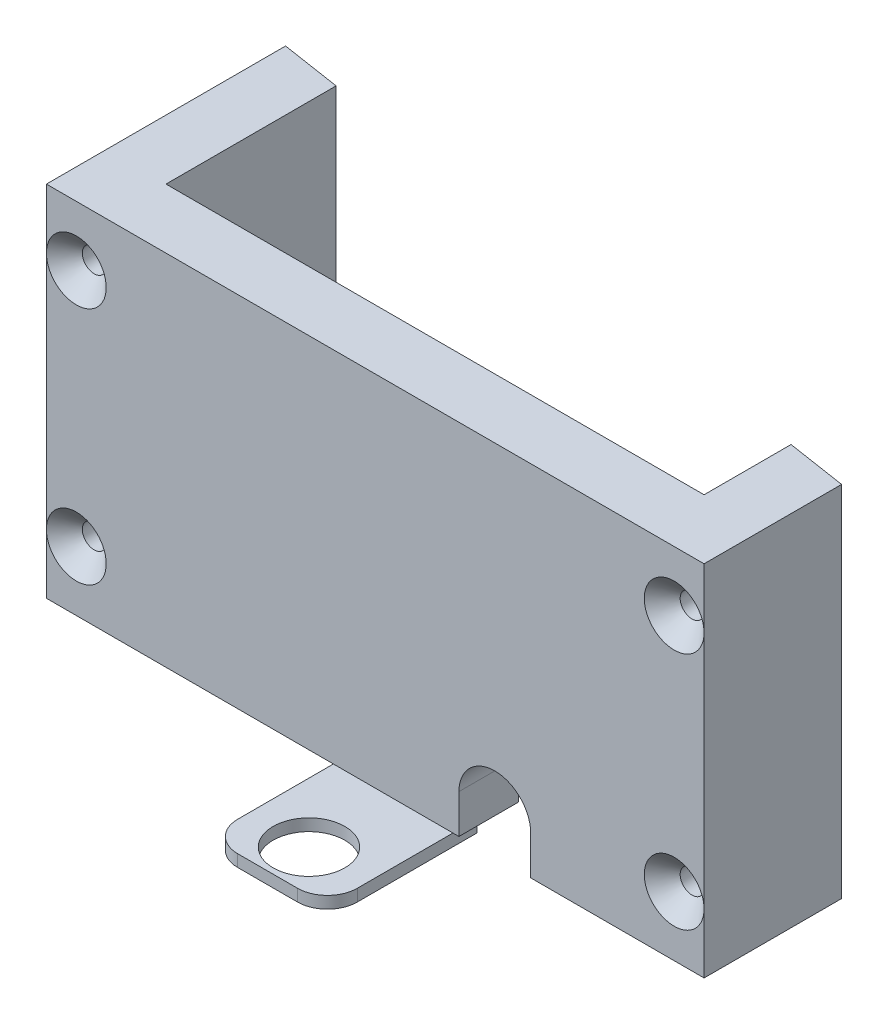
SolidWorks part; units mm, degrees
ref_plane "Plan de face" through (0, 0, 0) normal (0, 0, 1) x (1, 0, 0)
ref_plane "Plan de dessus" through (0, 0, 0) normal (0, 1, 0) x (1, 0, 0)
ref_plane "Plan de droite" through (0, 0, 0) normal (1, 0, 0) x (0, 0, -1)
sketch "Esquisse1" plane through (0, 0, 0) normal (0, 0, 1) x (1, 0, 0)
  line L1 (0, 0) -> (110, 0)
  line L2 (0, 0) -> (0, -60)
  line L3 (0, -60) -> (110, -60)
  line L4 (110, 0) -> (110, -60)
  dimension "D1" = 110
  dimension "D2" = 60
extrude "Boss.-Extru.1" add sketch "Esquisse1" along normal blind 10
sketch "Esquisse3" plane through (0, 0, 10) normal (0, 0, 1) x (1, 0, 0)
  line L0 (81, -53.5) -> (81, -60)
  line L3 (73.1533, -49.5) -> (73.1533, -57.5) construction
  line L4 (84.5, -49.5) -> (24.5, -49.5) construction
  line L5 (84.5, -57.5) -> (24.5, -57.5) construction
  line L7 (110, -60) -> (110, 0) construction
  line L8 (0, -60) -> (110, -60) construction
  line L9 (81, -60) -> (69, -60)
  line L10 (69, -60) -> (69, -53.5)
  arc A1 (81, -53.5) -> (69, -53.5) centre (75, -53.5) ccw
  dimension "D1" = 12
  dimension "D3" = 35
sketch "Esquisse7" plane through (0, 0, 0) normal (0, 0, -1) x (-1, 0, 0)
  line L0 (0, -60) -> (-110, -60) construction
  line L1 (-110, 0) -> (-100, 0)
  line L2 (-110, 0) -> (-110, -60)
  line L3 (-110, -60) -> (-100, -60)
  line L4 (-100, 0) -> (-100, -60)
  line L6 (0, 0) -> (-10, 0)
  line L7 (0, 0) -> (0, -60)
  line L8 (0, -60) -> (-10, -60)
  line L9 (-10, 0) -> (-10, -60)
  dimension "D1" = 10
extrude "Boss.-Extru.3" add sketch "Esquisse7" along normal blind 30
sketch "Esquisse8" plane through (0, -60, 0) normal (0, -1, 0) x (1, 0, 0)
  line L4 (0, -30) -> (110, -13)
  line L5 (110, 10) -> (110, -30) construction
  line L6 (110, -13) -> (110, -30)
  line L7 (110, -30) -> (0, -30)
  dimension "D1" = 17
extrude "Enlèv. mat.-Extru.2" cut sketch "Esquisse8" against normal blind 81
sketch "Esquisse9" plane through (0, 0, 10) normal (0, 0, 1) x (1, 0, 0)
  line L0 (0, 0) -> (0, -60) construction
  line L1 (110, -60) -> (110, 0) construction
  line L2 (110, 0) -> (0, 0) construction
  line L3 (0, -60) -> (110, -60) construction
  circle A0 centre (5, -10) radius 2
  circle A1 centre (105, -10) radius 2
  circle A2 centre (105, -50) radius 2
  circle A3 centre (5, -50) radius 2
  dimension "D1" = 4
  dimension "D2" = 5
  dimension "D3" = 5
  dimension "D4" = 5
  dimension "D5" = 5
  dimension "D6" = 10
  dimension "D7" = 10
  dimension "D8" = 10
  dimension "D9" = 10
extrude "Enlèv. mat.-Extru.3" cut sketch "Esquisse9" against normal through all
chamfer "Chanfrein1" distance 3 angle 45 4 edges at (107, -10, 10) (107, -50, 10) (7, -50, 10) (7, -10, 10)
extrude "Enlèv. mat.-Extru.4" cut sketch "Esquisse3" against normal blind 10
ref_plane "Plan1" through (85, 0, 0) normal (-1, 0, 0) x (0, 0, 1)
sketch "Esquisse10" plane through (85, 0, 0) normal (-1, 0, 0) x (0, 0, 1)
  line L3 (-5.5213, -1.3552) -> (-6.7343, -1.3552)
  line L8 (0, -24.6816) -> (0, -42)
  line L9 (0, -60) -> (0, 0) construction
  line L10 (0, -42) -> (-7.5577, -42)
  line L11 (-7.5577, -42) -> (-7.5577, -62.3933)
  line L12 (-7.5577, -62.3933) -> (-9.5577, -62.3933)
  line L13 (-9.5577, -62.3933) -> (-9.5577, -40)
  line L14 (-9.5577, -40) -> (-2, -40)
  line L15 (-2, -40) -> (-2, -24.6816)
  line L16 (-2, -24.6816) -> (0, -24.6816)
  line L17 (-14.5455, -60) -> (0, -60) construction
  dimension "D1" = 2
  dimension "D2" = 2
  dimension "D3" = 2
  dimension "D4" = 22.3933
  dimension "D5" = 18
extrude "Boss.-Extru.4" add sketch "Esquisse10" along normal blind 20 separate body contours L16 L15 L14 L13 L12 L11 L10 L8 region at (85, -33.3408, -0.389)
sketch "Esquisse11" plane through (0, 0, -7.5577) normal (0, 0, 1) x (1, 0, 0)
  circle A0 centre (75, -53.5) radius 6
  dimension "D1" = 12
extrude "Enlèv. mat.-Extru.6" cut sketch "Esquisse11" against normal blind 23
ref_plane "Plan2" through (40, 0, 0) normal (1, 0, 0) x (0, 0, -1)
sketch "Esquisse12" plane through (40, 0, 0) normal (1, 0, 0) x (0, 0, -1)
  line L0 (0, -48) -> (0, -68)
  line L1 (0, -60) -> (0, 0) construction
  line L2 (0, -68) -> (-23, -68)
  line L3 (-23, -68) -> (-23, -70)
  line L4 (-23, -70) -> (2, -70)
  line L5 (2, -70) -> (2, -48)
  line L6 (2, -48) -> (0, -48)
  line L7 (0, -60) -> (-10, -60) construction
  dimension "D1" = 2
  dimension "D2" = 2
  dimension "D3" = 20
  dimension "D4" = 8
  dimension "D5" = 25
extrude "Boss.-Extru.5" add sketch "Esquisse12" along normal blind 20 separate body
sketch "Esquisse13" plane through (0, -70, 0) normal (0, -1, 0) x (1, 0, 0)
  circle A0 centre (50, 16.0823) radius 6
extrude "Enlèv. mat.-Extru.7" cut sketch "Esquisse13" against normal blind 20
fillet "Congé1" radius 5 2 edges at (40, -69, 23) (60, -69, 23)
fillet "Congé2" radius 5 2 edges at (85, -62.3933, -8.5577) (65, -62.3933, -8.5577)
